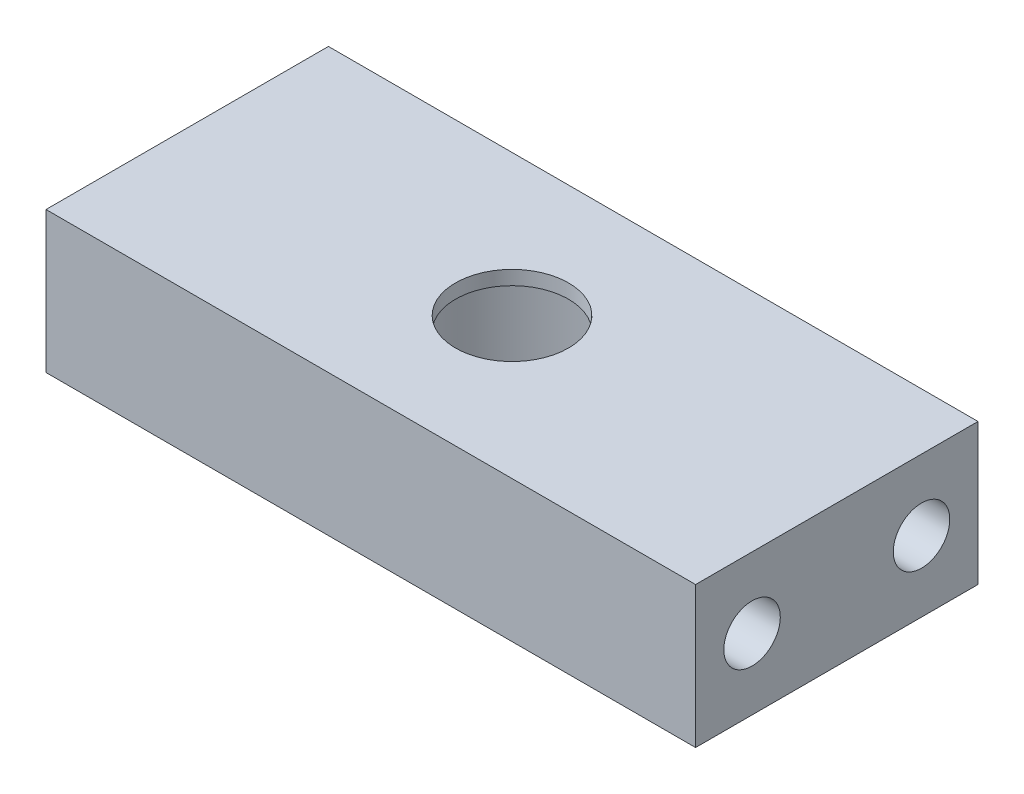
SolidWorks part; units mm, degrees
material "ABS"
ref_plane "Front Plane" through (0, 0, 0) normal (0, 0, 1) x (1, 0, 0)
ref_plane "Top Plane" through (0, 0, 0) normal (0, 1, 0) x (1, 0, 0)
ref_plane "Right Plane" through (0, 0, 0) normal (1, 0, 0) x (0, 0, -1)
sketch "Sketch1" plane through (0, 0, 0) normal (0, 0, 1) x (1, 0, 0)
  line L0 (0, 0) -> (0, -174.625)
  line L1 (0, -174.625) -> (171.45, -174.625)
  line L2 (171.45, -174.625) -> (171.45, 0)
  line L3 (171.45, 0) -> (158.75, 0)
  line L4 (158.75, 0) -> (158.75, -142.875)
  line L5 (158.75, -142.875) -> (12.7, -142.875)
  line L6 (12.7, -142.875) -> (12.7, 0)
  line L7 (12.7, 0) -> (0, 0)
  dimension "D1" = 171.45
  dimension "D2" = 12.7
  dimension "D3" = 31.75
  dimension "D4" = 174.625
extrude "Boss-Extrude1" add sketch "Sketch1" along normal blind 88.9
sketch "Sketch2" plane through (0, -142.875, 0) normal (0, 1, 0) x (1, 0, 0)
  line L0 (158.75, -88.9) -> (158.75, 0) construction
  line L1 (12.7, 0) -> (158.75, 0)
  line L2 (12.7, 0) -> (12.7, -25.4)
  line L3 (12.7, -25.4) -> (158.75, -25.4)
  line L4 (158.75, 0) -> (158.75, -25.4)
  line L5 (158.75, -88.9) -> (12.7, -88.9) construction
  line L6 (0, -50.8) -> (71.8503, -85.7079)
  line L9 (85.725, 0) -> (85.725, -57.15) construction
  line L10 (171.45, -50.8) -> (99.5997, -85.7079)
  line L12 (0, -50.8) -> (171.45, -50.8) construction
  line L13 (171.45, -50.8) -> (171.45, -88.9)
  line L14 (171.45, -88.9) -> (0, -88.9)
  line L15 (0, -88.9) -> (0, -50.8)
  circle A0 centre (85.725, -57.15) radius 31.75
  line M10 (158.75, 0) -> (12.7, 0)
  line M11 (12.7, 0) -> (12.7, -88.9)
  line M13 (158.75, -88.9) -> (158.75, 0)
  dimension "D3" = 63.5
  dimension "D1" = 63.5
  dimension "D2" = 38.1
extrude "Cut-Extrude2" cut sketch "Sketch2" against normal through all both and the other way through all contours L3 M11 M13 M10 region at (85.725, -142.875, 12.7)
sketch "Sketch3" plane through (0, -174.625, 0) normal (0, -1, 0) x (1, 0, 0)
  circle A2 centre (85.725, 57.15) radius 28.575
  dimension "D1" = 57.15
extrude "Cut-Extrude5" cut sketch "Sketch3" against normal offset from surface (28.575 mm away) 3.175 up to face at (85.725, -142.875, 57.15)
sketch "Sketch4" plane through (0, -146.05, 0) normal (0, -1, 0) x (1, 0, 0)
  circle A0 centre (85.725, 57.15) radius 28.575 construction
  circle A1 centre (85.725, 57.15) radius 28.575 construction
  circle A2 centre (85.725, 57.15) radius 12.7
  dimension "D1" = 25.4
extrude "Cut-Extrude6" cut sketch "Sketch4" against normal through all both and the other way through all
sketch "Sketch5" plane through (171.45, 0, 0) normal (1, 0, 0) x (0, 0, -1)
  line L0 (-88.9, 0) -> (0, 0) construction
  line L1 (-44.45, -142.875) -> (-69.85, -142.875) construction
  line L2 (-44.45, -142.875) -> (-69.85, -142.875) construction
  line L3 (-57.15, -142.875) -> (-57.15, 0) construction
  line L4 (-71.7453, -22.1194) -> (-39.2695, -98.0259)
  line L5 (-42.5547, -9.6306) -> (-2.0475, -104.3089)
  line L6 (-50.8, -142.875) -> (-39.5832, -118.7117)
  line L8 (-88.9, -174.625) -> (-88.9, 0) construction
  line L9 (-25.4, -174.625) -> (-2.3613, -124.9947)
  line L11 (-50.8, -142.875) -> (-88.9, -142.875)
  line L12 (0, -174.625) -> (0, 0) construction
  line L13 (-88.9, -174.625) -> (0, -174.625) construction
  line L14 (-25.4, -174.625) -> (0, -174.625)
  line L15 (0, -174.625) -> (0, 0)
  line L16 (0, 0) -> (-88.9, 0)
  line L17 (-88.9, 0) -> (-88.9, -142.875)
  line L18 (-25.4, -174.625) -> (-25.4, -142.875) construction
  line L19 (-25.4, -174.625) -> (-25.4, -142.875) construction
  circle A0 centre (-57.15, -15.875) radius 15.875
  arc A3 (-2.3613, -124.9947) -> (-2.0475, -104.3089) centre (-25.4, -114.3) ccw
  arc A5 (-39.5832, -118.7117) -> (-39.2695, -98.0259) centre (-62.622, -108.017) ccw
  line M9 (-88.9, -174.625) -> (0, -174.625)
  line M10 (0, -174.625) -> (0, 0)
  line M11 (0, 0) -> (-88.9, 0)
  line M12 (-88.9, 0) -> (-88.9, -174.625)
  dimension "D1" = 31.75
  dimension "D2" = 25.4
  dimension "D4" = 25.4
  dimension "D5" = 34.858
  dimension "D3" = 60.325
  dimension "D6" = 38.1
extrude "Cut-Extrude7" cut sketch "Sketch5" against normal through all both and the other way through all contours L4 A0 L16 M12 | A3 L15 A0 L5 M11 | A3 M9 M10 region at (171.45, -83.8741, 69.1874) region at (171.45, -36.1581, 15.7918) region at (171.45, -156.268, 8.4409)
sketch "Sketch6" plane through (171.45, 0, 0) normal (1, 0, 0) x (0, 0, -1)
  circle A0 centre (-57.15, -15.875) radius 9.525
  arc A1 (-42.5547, -9.6306) -> (-71.7453, -22.1194) centre (-57.15, -15.875) ccw construction
  dimension "D1" = 6.35
extrude "Cut-Extrude8" cut sketch "Sketch6" against normal up to surface (12.7 mm away) and the other way through all up to face at (158.75, -102.6264, 33.4448)
sketch "Sketch7" plane through (12.7, 0, 0) normal (1, 0, 0) x (0, 0, -1)
  circle A0 centre (-57.15, -15.875) radius 9.525 construction
  circle A1 centre (-57.15, -15.875) radius 9.525 construction
  circle A2 centre (-57.15, -15.875) radius 6.35
  dimension "D1" = 12.7
extrude "Cut-Extrude9" cut sketch "Sketch7" against normal up to surface (12.7 mm away) up to face at (0, -109.8263, 45.3403)
sketch "Sketch8" plane through (171.45, 0, 0) normal (1, 0, 0) x (0, 0, -1)
  line L0 (-88.9, -174.625) -> (-25.4, -174.625) construction
  line L1 (-50.8, -142.875) -> (-88.9, -142.875)
  line L2 (-88.9, -174.625) -> (-25.4, -174.625) construction
  line L4 (-44.45, -165.1) -> (-44.45, -152.4) construction
  line L5 (-44.45, -165.1) -> (-31.75, -165.1) construction
  line L8 (-31.75, -165.1) -> (-31.75, -152.4) construction
  line L9 (-31.75, -152.4) -> (-44.45, -152.4) construction
  line L12 (-88.9, -142.875) -> (-88.9, -174.625)
  line L13 (-88.9, -174.625) -> (-25.4, -174.625)
  line L14 (-2.0475, -104.3089) -> (-42.5547, -9.6306)
  line L16 (-2.0475, -104.3089) -> (-42.5547, -9.6306)
  line L17 (-88.9, -142.875) -> (-88.9, -174.625)
  line L18 (-88.9, -174.625) -> (-25.4, -174.625)
  line L24 (-88.9, -174.625) -> (-25.4, -174.625) construction
  line L26 (-82.55, -158.75) -> (-31.75, -158.75) construction
  line L27 (-82.55, -152.4) -> (-69.85, -152.4) construction
  line L28 (-71.7453, -22.1194) -> (-39.2695, -98.0259)
  line L30 (-71.7453, -22.1194) -> (-39.2695, -98.0259)
  line L32 (-88.9, -142.875) -> (-88.9, -174.625) construction
  line L34 (-25.4, -174.625) -> (-2.3613, -124.9947)
  line L35 (-25.4, -174.625) -> (-2.3613, -124.9947)
  line L36 (-82.55, -152.4) -> (-82.55, -165.1) construction
  line L37 (-39.5832, -118.7117) -> (-50.8, -142.875)
  line L38 (-39.5832, -118.7117) -> (-50.8, -142.875)
  line L39 (-50.8, -142.875) -> (-88.9, -142.875)
  line L40 (-50.8, -142.875) -> (-88.9, -142.875) construction
  line L41 (-82.55, -165.1) -> (-69.85, -165.1) construction
  line L42 (-69.85, -152.4) -> (-69.85, -165.1) construction
  line L43 (-76.2, -152.4) -> (-76.2, -165.1) construction
  line L44 (-38.1, -152.4) -> (-38.1, -165.1) construction
  circle A0 centre (-76.2, -158.75) radius 6.35
  circle A1 centre (-38.1, -158.75) radius 6.35
  arc A3 (-2.3613, -124.9947) -> (-2.0475, -104.3089) centre (-25.4, -114.3) ccw
  arc A4 (-2.3613, -124.9947) -> (-2.0475, -104.3089) centre (-25.4, -114.3) ccw
  arc A5 (-42.5547, -9.6306) -> (-71.7453, -22.1194) centre (-57.15, -15.875) ccw
  arc A9 (-42.5547, -9.6306) -> (-71.7453, -22.1194) centre (-57.15, -15.875) ccw
  arc A10 (-39.5832, -118.7117) -> (-39.2695, -98.0259) centre (-62.622, -108.017) ccw
  arc A11 (-39.5832, -118.7117) -> (-39.2695, -98.0259) centre (-62.622, -108.017) ccw
  dimension "D3" = 12.7
  dimension "D4" = 12.7
  dimension "D5" = 6.35
  dimension "D1" = 9.525
  dimension "D6" = 6.35
  dimension "D2" = 0
sketch "Sketch12" plane through (12.7, 0, 0) normal (1, 0, 0) x (0, 0, -1)
  circle A0 centre (-57.15, -15.875) radius 12.7
  dimension "D1" = 25.4
extrude "Cut-Extrude13" cut sketch "Sketch12" against normal blind 3.175
sketch "Sketch14" plane through (12.7, 0, 0) normal (1, 0, 0) x (0, 0, -1)
  circle A0 centre (-53.7708, -24.7804) radius 1.5875
  circle A1 centre (-66.5519, -14.3488) radius 1.5875
  circle A2 centre (-51.1273, -8.4958) radius 1.5875
extrude "Cut-Extrude14" cut sketch "Sketch14" against normal through all both and the other way through all
extrude "Cut-Extrude15" cut sketch "Sketch8" against normal up to surface (12.7 mm away) contours L30 A11 L38 L1 L12 L13 L35 A4 L16 A9 up to face at (158.75, -15.875, 57.15)
extrude "Cut-Extrude16" cut sketch "Sketch8<4>" against normal blind 19.05 from surface contours A0 | A1 starting at face at (158.75, -158.75, 57.15)
sketch "Sketch8<4>" plane through (171.45, 0, 0) normal (1, 0, 0) x (0, 0, -1) same geometry as "Sketch8"
extrude "Cut-Extrude18" cut sketch "Sketch8<9>" against normal up to surface (171.45 mm away) from surface contours L16 A9 L30 A11 L38 L1 L12 L13 L35 A4 up to face at (0, -24.7804, 52.1833) starting at face at (12.7, -15.875, 44.45)
sketch "Sketch8<9>" plane through (171.45, 0, 0) normal (1, 0, 0) x (0, 0, -1) same geometry as "Sketch8"
extrude "Cut-Extrude19" cut sketch "Sketch8<10>" along normal blind 19.05 from surface contours A0 | A1 starting at face at (12.7, -158.75, 57.15)
sketch "Sketch8<10>" plane through (171.45, 0, 0) normal (1, 0, 0) x (0, 0, -1) same geometry as "Sketch8"
sketch "Sketch15" plane through (0, -174.625, 0) normal (0, -1, 0) x (1, 0, 0)
  line L0 (140.97, 88.9) -> (140.97, 25.4) construction
  line L1 (12.7, 88.9) -> (158.75, 88.9) construction
  line L2 (12.7, 25.4) -> (158.75, 25.4) construction
  line L3 (12.7, 25.4) -> (12.7, 88.9) construction
  line L4 (12.7, 57.15) -> (158.75, 57.15) construction
  line L5 (158.75, 25.4) -> (158.75, 88.9) construction
  circle A0 centre (140.97, 73.025) radius 6.35
  circle A1 centre (140.97, 41.275) radius 6.35
  dimension "D2" = 12.7
  dimension "D1" = 128.27
  dimension "D3" = 15.875
extrude "Cut-Extrude20" cut sketch "Sketch15" against normal blind 19.05
chamfer "Chamfer1" distance 2 angle 45 1 edges at (114.3, -174.625, 57.15)
